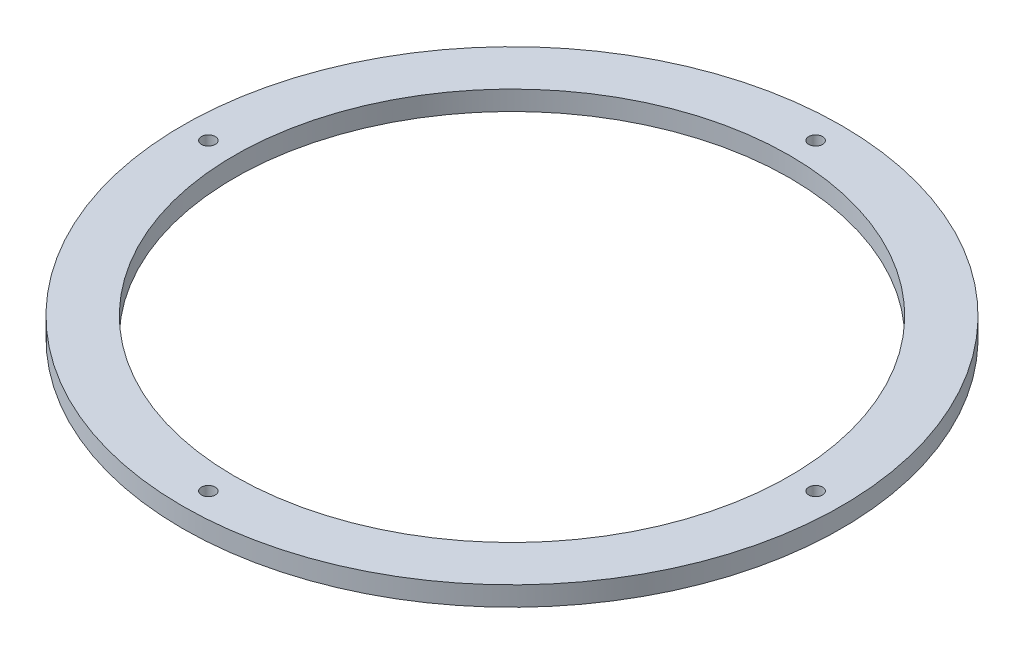
SolidWorks part; units mm, degrees
material "Pine"
ref_plane "Front Plane" through (0, 0, 0) normal (0, 0, 1) x (1, 0, 0)
ref_plane "Top Plane" through (0, 0, 0) normal (0, 1, 0) x (1, 0, 0)
ref_plane "Right Plane" through (0, 0, 0) normal (1, 0, 0) x (0, 0, -1)
sketch "Sketch1" plane through (0, 0, 0) normal (0, 1, 0) x (1, 0, 0)
  circle A0 centre (0, 0) radius 161.4
  circle A1 centre (0, 0) radius 136
  dimension "D1" = 25.4
  dimension "D2" = 272
extrude "Boss-Extrude1" add sketch "Sketch1" along normal blind 9.525
sketch "Sketch2" plane through (0, 9.525, 0) normal (0, 1, 0) x (1, 0, 0)
  line L0 (0, 0) -> (0, -161.4) construction
  circle A0 centre (0, 0) radius 161.4 construction
  point P6 (0, -148.7)
  dimension "D1" = 12.7
hole_wizard "1/4 Clearance Hole1" positions "Sketch2" profile "Sketch3" hole size "1/4" standard "ANSI Inch" end condition through all
sketch "Sketch3" plane through (0, 9.525, 148.7) normal (1, 0, 0) x (0, 0, 1)
  line L0 (0, 0) -> (0, 9.525)
  line L1 (0, 9.525) -> (3.3782, 9.525)
  line L2 (3.3782, 9.525) -> (3.3782, 0)
  line L5 (3.3782, 0) -> (0, 0)
  line L11 (0, -6.35) -> (0, 107.95) construction
  dimension "Thru Hole Dia." = 6.7564
  dimension "Thru Hole Depth" = 9.525
pattern_circular "CirPattern1" count 4 every 90 about axis through (0, 9.525, 0) along (0, -1, 0) of "1/4 Clearance Hole1"
